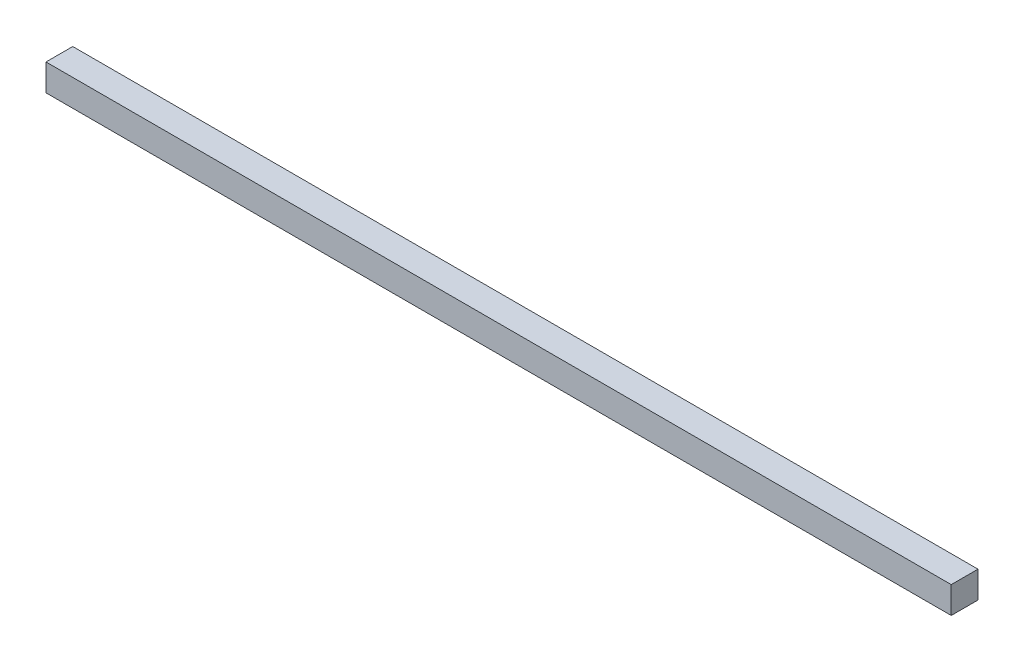
SolidWorks part; units mm, degrees
ref_plane "Спереди" through (0, 0, 0) normal (0, 0, 1) x (1, 0, 0)
ref_plane "Сверху" through (0, 0, 0) normal (0, 1, 0) x (1, 0, 0)
ref_plane "Справа" through (0, 0, 0) normal (1, 0, 0) x (0, 0, -1)
other "Configuration Table"
sketch "Эскиз1" plane through (0, 0, 0) normal (1, 0, 0) x (0, 0, -1)
  line L1 (0, 0) -> (9, 0)
  line L2 (0, 0) -> (0, 9)
  line L3 (0, 9) -> (9, 9)
  line L4 (9, 0) -> (9, 9)
extrude "Бобышка-Вытянуть1" add sketch "Эскиз1" along normal blind 304.5
